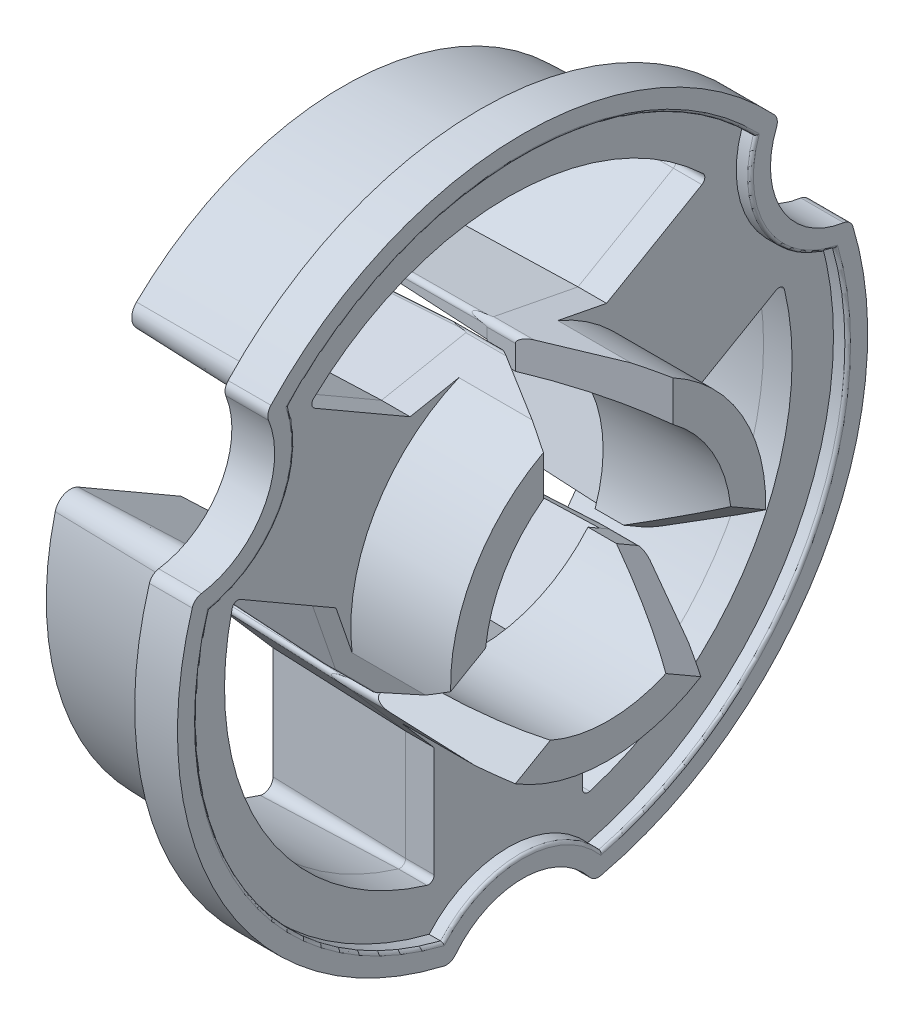
SolidWorks part; units mm, degrees
ref_plane "前视基准面" through (0, 0, 0) normal (0, 0, 1) x (1, 0, 0)
ref_plane "上视基准面" through (0, 0, 0) normal (0, 1, 0) x (1, 0, 0)
ref_plane "右视基准面" through (0, 0, 0) normal (1, 0, 0) x (0, 0, -1)
sketch "草图1" plane through (0, 0, 0) normal (0, 0, 1) x (1, 0, 0)
  line L0 (-12.1146, 0) -> (14.7387, 0) construction
  line L1 (0, 16.6473) -> (0, -11.3565) construction
  line L2 (0, 12.1) -> (1, 12.1)
  line L5 (1, 12.1) -> (1, 4.1)
  line L6 (1, 4.1) -> (0, 4.1)
  line L7 (0, 4.1) -> (0, 12.1)
  dimension "D1" = 24.2
  dimension "D2" = 1
  dimension "D3" = 8.2
revolve "旋转1" add sketch "草图1" angle 360 about L0
sketch "草图11" plane through (0, 0, 0) normal (-1, 0, 0) x (0, 0, 1)
  line L0 (-14.4614, 0) -> (15.7146, 0) construction
  line L1 (0, 13.2082) -> (0, -14.2305) construction
  line L2 (-3.053, -0.78) -> (1.6654, -0.78) construction
  line L3 (0, 0) -> (-14.7032, 8.4889) construction
  line L4 (0, 0) -> (15.6195, 9.0179) construction
  line L5 (0, 0) -> (13.4467, -7.7635) construction
  line L6 (0.8755, -0.0436) -> (0.6755, -0.39) construction
  arc A0 (0, 4.5642) -> (-3.9527, -2.2821) centre (0.6755, -0.39) ccw
  arc A1 (3.9527, -2.2821) -> (0, 4.5642) centre (-0.6755, -0.39) ccw
  arc A2 (-3.9527, -2.2821) -> (3.9527, -2.2821) centre (0, 0.78) ccw
  point P7 (0, -0.78)
  point P23 (0, 0)
  dimension "D2" = 10
  dimension "D1" = 0.78
  dimension "D3" = 60
  dimension "D4" = 60
  dimension "D6" = 60
  dimension "D7" = 0.78
  dimension "D5" = 3
extrude "切除-拉伸5" cut sketch "草图11" against normal blind 10
sketch "草图2" plane through (0, 0, 0) normal (-1, 0, 0) x (0, 0, 1)
  line L0 (-16.221, 0) -> (19.4228, 0) construction
  line L1 (0, 16.0936) -> (0, -16.7209) construction
  line L2 (0, 0) -> (-14.0549, 8.1146) construction
  line L3 (0, 0) -> (15.0563, 8.6927) construction
  line L4 (-7.2036, 6.4684) -> (-3.5494, 4.3587)
  line L6 (-0.25, 5.6112) -> (-0.25, 5)
  line L7 (0.25, 5.6112) -> (0.25, 5)
  line L8 (3.5494, 4.3587) -> (0.25, 5)
  line L9 (7.2036, 6.4684) -> (3.5494, 4.3587)
  line L10 (3.4437, 4.9904) -> (0.85, 5.4946) construction
  line L11 (3.4437, 4.9904) -> (0.25, 5.6112)
  line L12 (6.7881, 6.9213) -> (3.4437, 4.9904)
  line L13 (-6.7881, 6.9213) -> (-3.4437, 4.9904)
  line L15 (-3.4437, 4.9904) -> (-0.85, 5.4946) construction
  line L16 (-0.85, 6.5945) -> (-0.85, 5.4946) construction
  line L17 (0.85, 6.8313) -> (0.85, 5.4946) construction
  line L18 (-6.9036, 6.988) -> (-3.4437, 4.9904) construction
  line L19 (0.25, 6.8313) -> (0.25, 5) construction
  line L20 (-0.25, 6.5945) -> (-0.25, 5) construction
  line L21 (6.9036, 6.988) -> (3.4437, 4.9904) construction
  line L22 (-3.5494, 4.3587) -> (-0.25, 5) construction
  line L23 (-3.5494, 4.3587) -> (-0.25, 5)
  line L24 (-3.4437, 4.9904) -> (-0.25, 5.6112)
  arc A0 (7.3407, 7.5774) -> (-7.3407, 7.5774) centre (0, 0) ccw
  circle A1 centre (0, 0) radius 4.1 construction
  arc A3 (7.2036, 6.4684) -> (7.3407, 7.5774) centre (6.8536, 7.0746) ccw
  arc A4 (-7.2036, 6.4684) -> (-7.3407, 7.5774) centre (-6.8536, 7.0746) cw
  arc A6 (6.8253, 7.24) -> (-6.8253, 7.24) centre (0, 0) ccw
  arc A7 (6.8253, 7.24) -> (6.7881, 6.9213) centre (6.6881, 7.0945) cw
  arc A8 (6.9232, 7.1465) -> (-6.9232, 7.1465) centre (0, 0) ccw construction
  arc A9 (-6.7881, 6.9213) -> (-6.8253, 7.24) centre (-6.6881, 7.0945) cw
  arc A10 (-6.9036, 6.988) -> (-6.9232, 7.1465) centre (-6.8536, 7.0746) cw construction
  arc A11 (6.9036, 6.988) -> (6.9232, 7.1465) centre (6.8536, 7.0746) ccw construction
  dimension "D1" = 21.1
  dimension "D8" = 0.7
  dimension "D11" = 0.2
  dimension "D12" = 0.2
  dimension "D14" = 0.6
  dimension "D7" = 5
  dimension "D5" = 8.2
  dimension "D2" = 60
  dimension "D3" = 60
  dimension "D4" = 2
  dimension "D6" = 0.25
  dimension "D9" = 2
  dimension "D13" = 0.6
  dimension "D15" = 139
  dimension "D17" = 41
  dimension "D10" = 139
extrude "凸台-拉伸1" add sketch "草图2" along normal blind 4.8 draft 1.8
pattern_circular "阵列(圆周)1" count 3 over 360 about axis through (-12.1146, 0, 0) along (-1, 0, 0) of "凸台-拉伸1"
sketch "草图3" plane through (0, 0, 0) normal (-1, 0, 0) x (0, 0, 1)
  line L0 (-15.829, 0) -> (17.3645, 0) construction
  line L1 (0, 16.96) -> (0, -16.96) construction
  line L20 (6.7881, 6.9213) -> (3.4437, 4.9904) construction
  line L21 (-3.4437, 4.9904) -> (-6.7881, 6.9213) construction
  line L22 (-0.25, 5) -> (-0.25, 5.6112) construction
  line L23 (-0.25, 5.6112) -> (-3.4437, 4.9904) construction
  line L24 (6.7881, 6.9213) -> (3.4437, 4.9904)
  line L25 (-3.4437, 4.9904) -> (-6.7881, 6.9213)
  line L26 (-0.25, 4.0924) -> (-0.25, 5.3686)
  line L27 (-0.4882, 5.5649) -> (-3.4437, 4.9904)
  line L28 (0.25, 5.6112) -> (0.25, 5) construction
  line L29 (3.4437, 4.9904) -> (0.25, 5.6112) construction
  line L30 (0.25, 5.3686) -> (0.25, 4.0924)
  line L31 (3.4437, 4.9904) -> (0.4882, 5.5649)
  arc A8 (6.7881, 6.9213) -> (6.8253, 7.24) centre (6.6881, 7.0945) ccw construction
  arc A9 (6.7881, 6.9213) -> (6.8253, 7.24) centre (6.6881, 7.0945) ccw
  arc A12 (6.8253, 7.24) -> (-6.8253, 7.24) centre (0, 0) ccw construction
  arc A13 (-6.8253, 7.24) -> (-6.7881, 6.9213) centre (-6.6881, 7.0945) ccw construction
  arc A14 (6.8253, 7.24) -> (-6.8253, 7.24) centre (0, 0) ccw
  arc A15 (-6.8253, 7.24) -> (-6.7881, 6.9213) centre (-6.6881, 7.0945) ccw
  arc A16 (0.4882, 5.5649) -> (0.25, 5.3686) centre (0.45, 5.3686) ccw
  arc A17 (-0.25, 5.3686) -> (-0.4882, 5.5649) centre (-0.45, 5.3686) ccw
  arc A18 (0.25, 4.0924) -> (-0.25, 4.0924) centre (0, 0) ccw
  dimension "D1" = 8.2
  dimension "D2" = 0.2
extrude "切除-拉伸1" cut sketch "草图3" against normal mid plane 14.8
pattern_circular "阵列(圆周)2" count 3 over 360 about axis through (0, 0, 0) along (-1, 0, 0) of "切除-拉伸1"
ref_axis "基准轴1" through (11.3461, 0, 0) along (-1, 0, 0)
sketch "草图13" plane through (1, 0, 0) normal (1, 0, 0) x (0, 0, -1)
  line L0 (-15.8465, 0) -> (17.3635, 0) construction
  line L1 (0, 13.439) -> (0, -14.4944) construction
  line L2 (0, 0) -> (-16.0018, 9.2386) construction
  line L3 (-0.4882, 5.5649) -> (-3.4437, 4.9904) construction
  line L4 (-0.4882, 5.5649) -> (-1.7335, 5.3229)
  line L5 (-0.25, 4.5236) -> (-0.25, 5.3686) construction
  line L6 (-0.25, 4.5236) -> (-0.25, 5.3686)
  line L9 (-4.7744, -2.4678) -> (-4.0426, -2.0453) construction
  line L10 (-4.7744, -2.4678) -> (-4.0426, -2.0453)
  line L13 (-5.4765, -1.1602) -> (-5.0635, -2.3597)
  arc A3 (-0.25, 5.3686) -> (-0.4882, 5.5649) centre (-0.45, 5.3686) ccw construction
  arc A4 (-0.25, 5.3686) -> (-0.4882, 5.5649) centre (-0.45, 5.3686) ccw
  arc A5 (-5.0635, -2.3597) -> (-4.7744, -2.4678) centre (-4.8744, -2.2946) ccw construction
  arc A6 (-5.0635, -2.3597) -> (-4.7744, -2.4678) centre (-4.8744, -2.2946) ccw
  arc A7 (-0.25, 4.5236) -> (-4.0426, -2.0453) centre (0.6755, -0.39) ccw construction
  arc A8 (-0.25, 4.5236) -> (-4.0426, -2.0453) centre (0.6755, -0.39) ccw
  arc A9 (-1.7335, 5.3229) -> (-5.4765, -1.1602) centre (0.6755, -0.39) ccw
  point P10 (-0.1755, 0.1013)
  point P11 (-0.2668, 5.5235)
  point P12 (-4.9169, -2.5306)
  dimension "D2" = 5
  dimension "D3" = 12.4
  dimension "D1" = 60
extrude "凸台-拉伸3" add sketch "草图13" along normal blind 3.5
pattern_circular "阵列(圆周)6" count 3 over 360 about axis through (-12.1146, 0, 0) along (-1, 0, 0) of "凸台-拉伸3"
sketch "草图5" plane through (0, 0, 0) normal (0, 1, 0) x (1, 0, 0)
  line L0 (-10.3596, 0) -> (16.169, 0) construction
  line L1 (0, -13.3133) -> (0, 14.2281) construction
  line L2 (1, -9.5779) -> (1, 3.3379) construction
  line L3 (1, -0.25) -> (4.8245, -2.4581)
  line L4 (1, 0.25) -> (4.8245, 2.4581)
  line L5 (1, -0.25) -> (1, 0.25)
  line L6 (4.8245, -2.4581) -> (4.8245, 2.4581)
  point P11 (1, 1.05)
  dimension "D1" = 1
  dimension "D2" = 0.25
  dimension "D3" = 30
extrude "切除-拉伸2" cut sketch "草图5" along normal blind 6.8 contours L3 L6 L4 L5
pattern_circular "阵列(圆周)3" count 3 over 360 about axis through (-12.1146, 0, 0) along (-1, 0, 0) of "切除-拉伸2"
sketch "草图7" plane through (0, 0, 0) normal (-1, 0, 0) x (0, 0, 1)
  line L0 (-14.5222, 0) -> (14.1954, 0) construction
  line L1 (0, 13.4113) -> (0, -13.444) construction
  line L2 (0, 0) -> (-14.3255, 8.2708) construction
  circle A0 centre (0, 0) radius 13.5 construction
  circle A1 centre (-11.6913, 6.75) radius 3
  dimension "D2" = 27
  dimension "D3" = 6
  dimension "D1" = 60
extrude "切除-拉伸4" cut sketch "草图7" against normal blind 6.8 contours A1
pattern_circular "阵列(圆周)5" count 3 over 360 about axis through (-12.1146, 0, 0) along (-1, 0, 0) of "切除-拉伸4"
sketch "草图9" plane through (1, 0, 0) normal (1, 0, 0) x (0, 0, -1)
  arc A0 (9.0039, 8.0833) -> (11.5023, 3.756) centre (11.6913, 6.75) ccw construction
  arc A1 (2.4984, -11.8393) -> (11.5023, 3.756) centre (0, 0) ccw construction
  arc A2 (2.4984, -11.8393) -> (-2.4984, -11.8393) centre (0, -13.5) ccw construction
  arc A3 (-11.5023, 3.756) -> (-2.4984, -11.8393) centre (0, 0) ccw construction
  arc A4 (-11.5023, 3.756) -> (-9.0039, 8.0833) centre (-11.6913, 6.75) ccw construction
  arc A5 (9.0039, 8.0833) -> (-9.0039, 8.0833) centre (0, 0) ccw construction
  arc A6 (9.0039, 8.0833) -> (11.5023, 3.756) centre (11.6913, 6.75) ccw
  arc A7 (2.4984, -11.8393) -> (11.5023, 3.756) centre (0, 0) ccw
  arc A8 (2.4984, -11.8393) -> (-2.4984, -11.8393) centre (0, -13.5) ccw
  arc A9 (-11.5023, 3.756) -> (-2.4984, -11.8393) centre (0, 0) ccw
  arc A10 (-11.5023, 3.756) -> (-9.0039, 8.0833) centre (-11.6913, 6.75) ccw
  arc A11 (9.0039, 8.0833) -> (-9.0039, 8.0833) centre (0, 0) ccw
  arc A12 (8.1859, 7.9341) -> (-8.1859, 7.9341) centre (0, 0) ccw
  arc A13 (-10.9641, 3.1222) -> (-8.1859, 7.9341) centre (-11.6913, 6.75) ccw
  arc A14 (-10.9641, 3.1222) -> (-2.7782, -11.0563) centre (0, 0) ccw
  arc A15 (2.7782, -11.0563) -> (-2.7782, -11.0563) centre (0, -13.5) ccw
  arc A16 (2.7782, -11.0563) -> (10.9641, 3.1222) centre (0, 0) ccw
  arc A17 (8.1859, 7.9341) -> (10.9641, 3.1222) centre (11.6913, 6.75) ccw
  dimension "D2" = 11.4
  dimension "D1" = 0.7
extrude "凸台-拉伸2" add sketch "草图9" along normal blind 0.5
fillet "圆角5" radius 0.1 6 edges at (1.5, 4.9, -8.487) (1.5, -5.7, -9.8727) (1.5, -9.8, 0) (1.5, -5.7, 9.8727) (1.5, 4.9, 8.487) (1.5, 11.4, 0)
fillet "圆角8" radius 0.15 6 edges at (-3.558, -3.0511, -4.5611) (-3.558, -2.4245, -4.9229) (-3.558, -2.4245, 4.9229) (-3.558, -3.0511, 4.5611) (-3.558, 5.4756, 0.3618) (-3.558, 5.4756, -0.3618)
fillet "圆角9" radius 0.4 6 edges at (0.75, -11.8393, -2.4984) (0.75, -11.8393, 2.4984) (0.75, 3.756, 11.5023) (0.75, 8.0833, 9.0039) (0.75, 3.756, -11.5023) (0.75, 8.0833, -9.0039)
